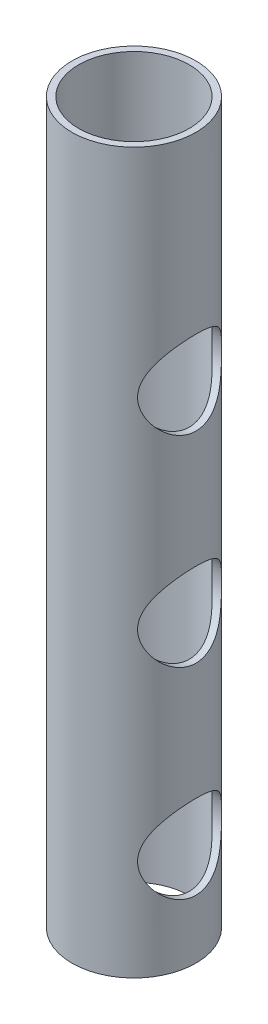
SolidWorks part; units mm, degrees
material "PTFE (general)"
ref_plane "Front Plane" through (0, 0, 0) normal (0, 0, 1) x (1, 0, 0)
ref_plane "Top Plane" through (0, 0, 0) normal (0, 1, 0) x (1, 0, 0)
ref_plane "Right Plane" through (0, 0, 0) normal (1, 0, 0) x (0, 0, -1)
sketch "Sketch1" plane through (0, 0, 0) normal (0, 1, 0) x (1, 0, 0)
  circle A0 centre (0, 0) radius 18.5
  circle A1 centre (0, 0) radius 16.5
  dimension "D1" = 2
  dimension "D2" = 33
extrude "Boss-Extrude1" add sketch "Sketch1" along normal blind 214.8
sketch "Sketch2" plane through (0, 0, 0) normal (1, 0, 0) x (0, 0, -1)
  line L0 (16.5, 214.8) -> (-16.5, 214.8) construction
  circle A0 centre (0, 150.1) radius 12.53
  circle A1 centre (0, 90.1) radius 12.53
  circle A2 centre (0, 30.1) radius 12.53
  dimension "D2" = 25.06
  dimension "D3" = 25.06
  dimension "D4" = 25.06
  dimension "D1" = 64.7
  dimension "D5" = 60
  dimension "D6" = 60
extrude "Cut-Extrude1" cut sketch "Sketch2" along normal through all
